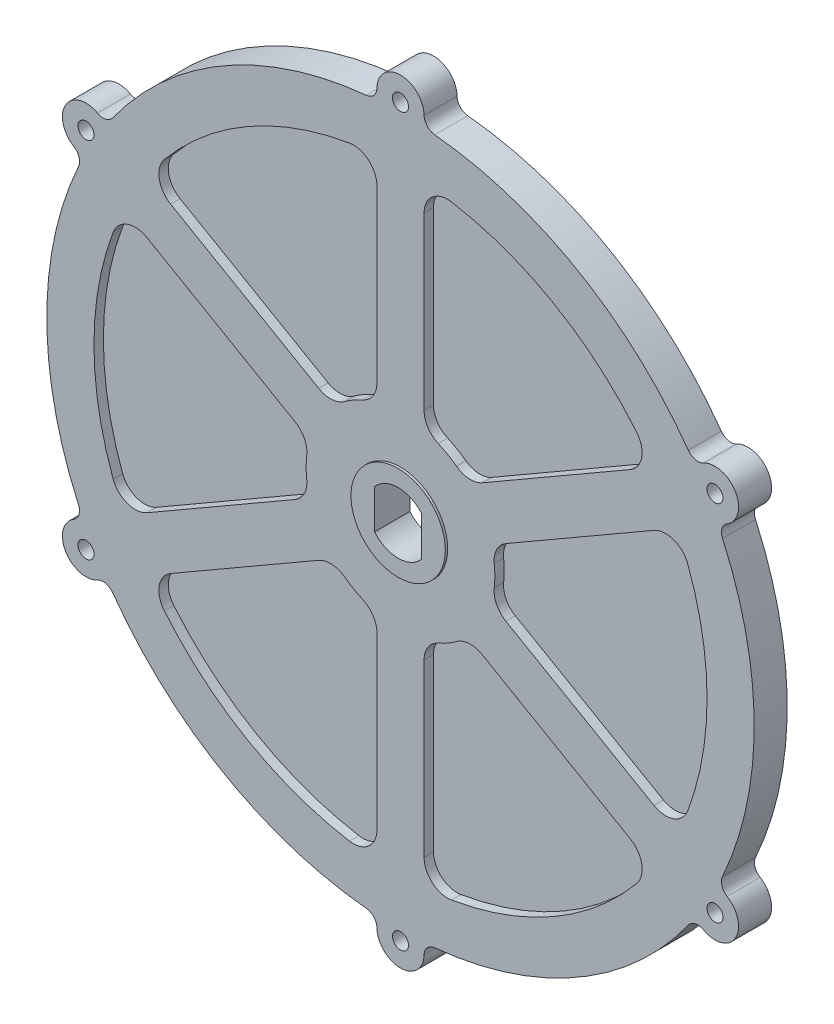
SolidWorks part; units mm, degrees
ref_plane "Front Plane" through (0, 0, 0) normal (0, 0, 1) x (1, 0, 0)
ref_plane "Top Plane" through (0, 0, 0) normal (0, 1, 0) x (1, 0, 0)
ref_plane "Right Plane" through (0, 0, 0) normal (1, 0, 0) x (0, 0, -1)
sketch "Sketch2" plane through (0, 0, 0) normal (0, 0, 1) x (1, 0, 0)
  line L0 (-5, 4.1533) -> (-5, -4.1533)
  line L1 (5, 4.1533) -> (5, -4.1533)
  circle A0 centre (0, 0) radius 75
  circle A1 centre (0, 0) radius 6.5
  dimension "D1" = 150
  dimension "D2" = 13
  dimension "D3" = 10
extrude "Boss-Extrude1" add sketch "Sketch2" along normal mid plane 7 contours A0 A1 | L0 A1 | L1 A1 region at (-5.6064, 0, 0) region at (5.6064, 0, 0) region at (-72.8787, 0, 0)
sketch "Sketch3" plane through (0, 0, 3.5) normal (0, 0, 1) x (1, 0, 0)
  circle A0 centre (0, 0) radius 10
  arc M2 (-5, 4.1533) -> (5, 4.1533) centre (0, 0) cw
  line M3 (5, 4.1533) -> (5, -4.1533)
  arc M4 (5, -4.1533) -> (-5, -4.1533) centre (0, 0) cw
  line M5 (-5, -4.1533) -> (-5, 4.1533)
  dimension "D1" = 20
extrude "Boss-Extrude2" add sketch "Sketch3" along normal blind 0.5 contours A0 M5 M2 M3 M4 region at (-9.7172, 0, 3.5)
sketch "Sketch4" plane through (0, 0, -3.5) normal (0, 0, 1) x (1, 0, 0)
  line L0 (5, 77) -> (5, 74.8331)
  line L1 (-5, 77) -> (-5, 74.8331)
  arc A0 (5, 77) -> (-5, 77) centre (0, 77) ccw
  circle A1 centre (0, 0) radius 75 construction
  circle A3 centre (0, 0) radius 75
  arc A4 (-5, 74.8331) -> (5, 74.8331) centre (0, 0) ccw
  circle M9 centre (0, 0) radius 75
  dimension "D1" = 5
  dimension "D2" = 77
  dimension "D3" = 0
extrude "Boss-Extrude3" add sketch "Sketch4" along normal up to surface (7 mm away) contours A0 L0 L1 M9 region at (0, 78.0396, -3.5) up to face at (10, 0, 3.5)
fillet "Fillet1" radius 2.5 2 edges at (-5, 74.8331, 0) (5, 74.8331, 0)
sketch "Sketch6" plane through (0, 0, -3.5) normal (0, 0, -1) x (-1, 0, 0)
  circle A0 centre (0, 77) radius 1.7
  arc A4 (4.9992, 77.0909) -> (-4.9992, 77.0909) centre (0, 77) ccw construction
  dimension "D1" = 3.4
extrude "Cut-Extrude1" cut sketch "Sketch6" against normal through all
pattern_circular "CirPattern1" count 6 over 360 about axis through (0, 0, -3.5) along (0, 0, 1) of "Boss-Extrude3", "Cut-Extrude1", "Fillet1"
sketch "Sketch7" plane through (0, 0, -3.5) normal (0, 0, -1) x (-1, 0, 0)
  line L0 (-5, 59.1608) -> (-5, 22.9129)
  line L1 (5, 59.1608) -> (5, 22.9129)
  line L2 (-5, 19.3649) -> (5, 19.3649) construction
  line L3 (48.7348, 33.9105) -> (17.3431, 15.7866)
  line L4 (53.7348, 25.2503) -> (22.3431, 7.1263)
  line L6 (53.7348, -25.2503) -> (22.3431, -7.1263)
  line L7 (48.7348, -33.9105) -> (17.3431, -15.7866)
  line L9 (5, -59.1608) -> (5, -22.9129)
  line L10 (-5, -59.1608) -> (-5, -22.9129)
  line L12 (-48.7348, -33.9105) -> (-17.3431, -15.7866)
  line L13 (-53.7348, -25.2503) -> (-22.3431, -7.1263)
  line L15 (-53.7348, 25.2503) -> (-22.3431, 7.1263)
  line L16 (-48.7348, 33.9105) -> (-17.3431, 15.7866)
  line L18 (0, 0) -> (8, 18.3303) construction
  line L19 (14.2705, 14.0126) -> (19.2705, 5.3523) construction
  line L20 (19.2705, -5.3523) -> (14.2705, -14.0126) construction
  line L21 (5, -19.3649) -> (-5, -19.3649) construction
  line L22 (-14.2705, -14.0126) -> (-19.2705, -5.3523) construction
  line L23 (-19.2705, 5.3523) -> (-14.2705, 14.0126) construction
  arc A0 (-8, 18.3303) -> (-11.8745, 16.0934) centre (0, 0) ccw
  arc A1 (-10.8333, 64.0909) -> (-50.0876, 41.4274) centre (0, 0) ccw
  arc A2 (5, 22.9129) -> (8, 18.3303) centre (10, 22.9129) ccw
  arc A3 (5, 59.1608) -> (10.8333, 64.0909) centre (10, 59.1608) cw
  arc A4 (-5, 59.1608) -> (-10.8333, 64.0909) centre (-10, 59.1608) ccw
  arc A5 (-5, 22.9129) -> (-8, 18.3303) centre (-10, 22.9129) cw
  arc A6 (22.3431, 7.1263) -> (19.8745, 2.2369) centre (24.8431, 2.7962) ccw
  arc A7 (53.7348, 25.2503) -> (60.921, 22.6635) centre (56.2348, 20.9201) cw
  arc A8 (48.7348, 33.9105) -> (50.0876, 41.4274) centre (46.2348, 38.2407) ccw
  arc A9 (17.3431, 15.7866) -> (11.8745, 16.0934) centre (14.8431, 20.1167) cw
  arc A10 (17.3431, -15.7866) -> (11.8745, -16.0934) centre (14.8431, -20.1167) ccw
  arc A11 (48.7348, -33.9105) -> (50.0876, -41.4274) centre (46.2348, -38.2407) cw
  arc A12 (53.7348, -25.2503) -> (60.921, -22.6635) centre (56.2348, -20.9201) ccw
  arc A13 (22.3431, -7.1263) -> (19.8745, -2.2369) centre (24.8431, -2.7962) cw
  arc A14 (-5, -22.9129) -> (-8, -18.3303) centre (-10, -22.9129) ccw
  arc A15 (-5, -59.1608) -> (-10.8333, -64.0909) centre (-10, -59.1608) cw
  arc A16 (5, -59.1608) -> (10.8333, -64.0909) centre (10, -59.1608) ccw
  arc A17 (5, -22.9129) -> (8, -18.3303) centre (10, -22.9129) cw
  arc A18 (-22.3431, -7.1263) -> (-19.8745, -2.2369) centre (-24.8431, -2.7962) ccw
  arc A19 (-53.7348, -25.2503) -> (-60.921, -22.6635) centre (-56.2348, -20.9201) cw
  arc A20 (-48.7348, -33.9105) -> (-50.0876, -41.4274) centre (-46.2348, -38.2407) ccw
  arc A21 (-17.3431, -15.7866) -> (-11.8745, -16.0934) centre (-14.8431, -20.1167) cw
  arc A22 (-17.3431, 15.7866) -> (-11.8745, 16.0934) centre (-14.8431, 20.1167) ccw
  arc A23 (-48.7348, 33.9105) -> (-50.0876, 41.4274) centre (-46.2348, 38.2407) cw
  arc A24 (-53.7348, 25.2503) -> (-60.921, 22.6635) centre (-56.2348, 20.9201) ccw
  arc A25 (-22.3431, 7.1263) -> (-19.8745, 2.2369) centre (-24.8431, 2.7962) cw
  arc A26 (11.8745, 16.0934) -> (8, 18.3303) centre (0, 0) ccw
  arc A27 (19.8745, -2.2369) -> (19.8745, 2.2369) centre (0, 0) ccw
  arc A28 (8, -18.3303) -> (11.8745, -16.0934) centre (0, 0) ccw
  arc A29 (-11.8745, -16.0934) -> (-8, -18.3303) centre (0, 0) ccw
  arc A30 (-19.8745, 2.2369) -> (-19.8745, -2.2369) centre (0, 0) ccw
  arc A31 (50.0876, 41.4274) -> (10.8333, 64.0909) centre (0, 0) ccw
  arc A32 (60.921, -22.6635) -> (60.921, 22.6635) centre (0, 0) ccw
  arc A33 (10.8333, -64.0909) -> (50.0876, -41.4274) centre (0, 0) ccw
  arc A34 (-50.0876, -41.4274) -> (-10.8333, -64.0909) centre (0, 0) ccw
  arc A35 (-60.921, 22.6635) -> (-60.921, -22.6635) centre (0, 0) ccw
  point P8 (0, 19.3649)
  dimension "D1" = 130
  dimension "D2" = 40
  dimension "D4" = 5
  dimension "D3" = 10
  dimension "D5" = 6
extrude "Cut-Extrude2" cut sketch "Sketch7" against normal blind 2
mirror "Mirror1" about plane through (0, 0, 0) normal (0, 0, 1) of "Cut-Extrude2"
